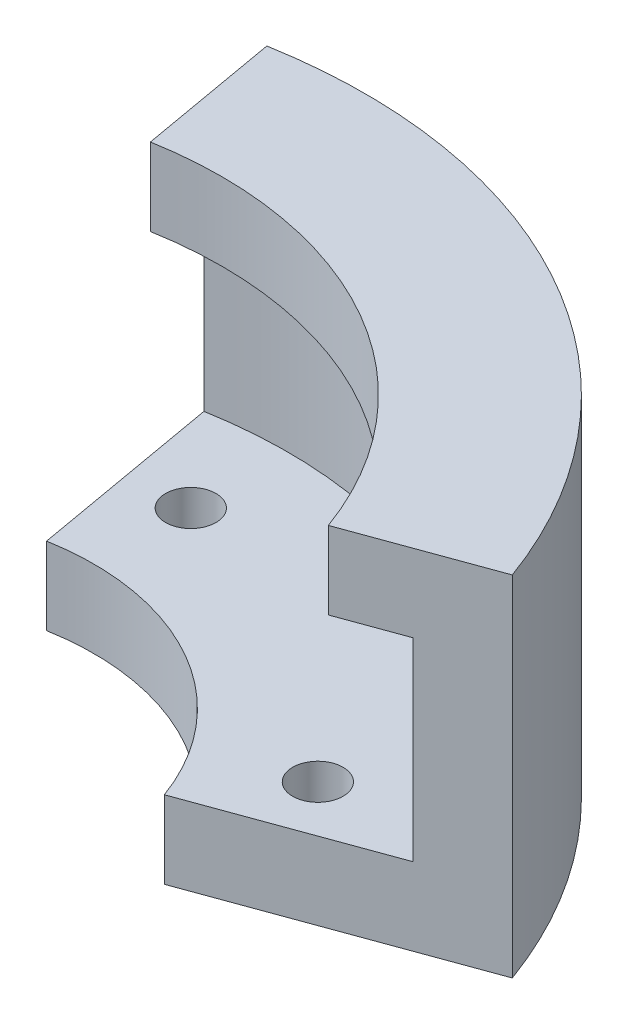
SolidWorks part; units mm, degrees
ref_plane "Front Plane" through (0, 0, 0) normal (0, 0, 1) x (1, 0, 0)
ref_plane "Top Plane" through (0, 0, 0) normal (0, 1, 0) x (1, 0, 0)
ref_plane "Right Plane" through (0, 0, 0) normal (1, 0, 0) x (0, 0, -1)
sketch "Sketch1" plane through (0, 0, 0) normal (0, 1, 0) x (1, 0, 0)
  line L0 (0, 29.083) -> (0, 16.383)
  line L1 (14.1881, 8.1915) -> (25.1866, 14.5415)
  line L2 (-5.0502, 28.6412) -> (-2.8449, 16.1341)
  line L3 (15.395, 5.6033) -> (27.3291, 9.947)
  circle A0 centre (0, 0) radius 29.083
  circle A1 centre (0, 0) radius 16.383
  circle A2 centre (0, 22.733) radius 1.651
  circle A3 centre (19.6874, 11.3665) radius 1.651
  dimension "D1" = 58.166
  dimension "D2" = 12.7
  dimension "D4" = 3.302
  dimension "D3" = 60
  dimension "D5" = 10
  dimension "D6" = 10
extrude "Boss-Extrude1" add sketch "Sketch1" along normal blind 12.7 contours A3 L1 A0 L0 A2 A1 | L0 A2 | L0 A2 | A2 L0 A0 L2 A1 | L1 A3 | L1 A3 | A3 L1 A1 L3 A0 region at (11.1691, 0, -19.3454) region at (-2.1537, 0, -23.2499) region at (0.7007, 0, -22.733) region at (-0.7007, 0, -22.733) region at (21.2119, 0, -9.7598) region at (20.0377, 0, -10.7597) region at (19.337, 0, -11.9733)
shell "Shell1" thickness 5.08 removed face at (-3.9475, 6.35, -22.3876) removed face at (7.2333, 6.35, -12.5284) removed face at (21.362, 6.35, -7.7751) outward yes
extrude "Cut-Extrude1" cut sketch "Sketch1<3>" against normal blind 12.192 contours A2 | A3
sketch "Sketch1<3>" plane through (0, 0, 0) normal (0, 1, 0) x (1, 0, 0) same geometry as "Sketch1"
sketch "Sketch2" plane through (0, 17.78, 0) normal (0, 1, 0) x (1, 0, 0)
  circle A0 centre (0, 0) radius 24.765
  dimension "D1" = 49.53
extrude "Cut-Extrude2" cut sketch "Sketch2" against normal up to surface (5.08 mm away) up to face at (10.0369, 12.7, -17.3844)
